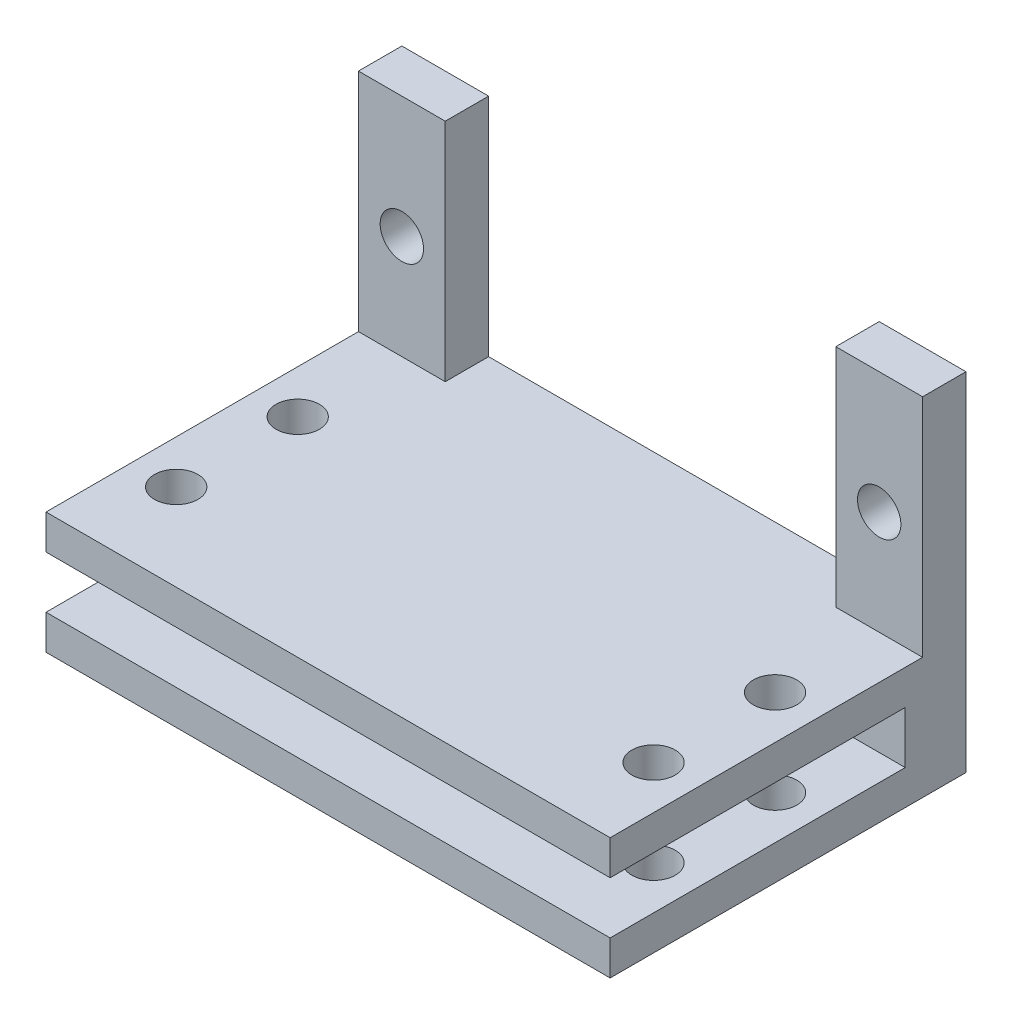
SolidWorks part; units mm, degrees
ref_plane "Front Plane" through (0, 0, 0) normal (0, 0, 1) x (1, 0, 0)
ref_plane "Top Plane" through (0, 0, 0) normal (0, 1, 0) x (1, 0, 0)
ref_plane "Right Plane" through (0, 0, 0) normal (1, 0, 0) x (0, 0, -1)
sketch "Sketch1" plane through (0, 0, 0) normal (0, 0, 1) x (1, 0, 0)
  line L0 (-16.25, 0) -> (-11.25, 0)
  line L1 (-16.25, 0) -> (-16.25, 13)
  line L2 (-16.25, 13) -> (-11.25, 13)
  line L3 (-11.25, 0) -> (-11.25, 13)
  line L8 (0, 12.0231) -> (0, -13.0504) construction
  line L9 (-16.25, 0) -> (16.25, 0)
  line L10 (-16.25, 0) -> (-16.25, -7)
  line L11 (-16.25, -7) -> (16.25, -7)
  line L13 (-16.25, -2) -> (16.25, -2)
  line L14 (-16.25, -2) -> (-16.25, -5)
  line L15 (-16.25, -5) -> (16.25, -5)
  line L17 (16.25, -2) -> (16.25, -5)
  line L18 (16.25, 0) -> (16.25, -7)
  line L19 (11.25, 0) -> (11.25, 13)
  line L20 (16.25, 13) -> (11.25, 13)
  line L21 (16.25, 0) -> (16.25, 13)
  line L22 (16.25, 0) -> (11.25, 0)
  circle A0 centre (-13.75, 6) radius 1.25
  circle A1 centre (13.75, 6) radius 1.25
  point P10 (13.75, 6)
  point P17 (0, -7)
  point P18 (0, 0)
  dimension "D7" = 6
  dimension "D8" = 2.5
  dimension "D1" = 7
  dimension "D2" = 2
  dimension "D3" = 5
  dimension "D4" = 13
  dimension "D5" = 2
  dimension "D6" = 11.25
  dimension "D9" = 2.5
extrude "Boss-Extrude1" add sketch "Sketch1" along normal blind 2.5 contours L0 L3 L2 L1 A0 | L9 L21 L20 L19 A1 region at (-16.1107, 6.5, 0) region at (11.3893, 6.5, 0)
extrude "Boss-Extrude2" add sketch "Sketch1<5>" along normal blind 20.5 contours L8 L9 L0 L10 L13 | L9 L8 L13 L18 | L8 L15 L10 L11 | L15 L8 L11 L18 region at (-8.125, -1, 0) region at (8.125, -1, 0) region at (-8.125, -6, 0) region at (8.125, -6, 0)
sketch "Sketch1<5>" plane through (0, 0, 0) normal (0, 0, 1) x (1, 0, 0) same geometry as "Sketch1"
extrude "Boss-Extrude3" add sketch "Sketch1<6>" along normal blind 3.5 contours L8 L13 L10 L15 | L13 L8 L15 L17 region at (-8.125, -3.5, 0) region at (8.125, -3.5, 0)
sketch "Sketch1<6>" plane through (0, 0, 0) normal (0, 0, 1) x (1, 0, 0) same geometry as "Sketch1"
sketch "Sketch2" plane through (0, 0, 0) normal (0, 1, 0) x (1, 0, 0)
  line L0 (0, -27.4164) -> (0, 3.5034) construction
  line L2 (16.25, -20.5) -> (16.25, -2.5) construction
  line L3 (-16.25, -20.5) -> (16.25, -20.5) construction
  circle A0 centre (13.75, -8.5) radius 1.25
  circle A1 centre (13.75, -15.5) radius 1.25
  circle A2 centre (-13.75, -15.5) radius 1.25
  circle A3 centre (-13.75, -8.5) radius 1.25
  dimension "D1" = 2.5
  dimension "D2" = 2.5
  dimension "D3" = 7
  dimension "D4" = 5
  dimension "D5" = 2.5
extrude "Cut-Extrude2" cut sketch "Sketch2" against normal through all both and the other way through all
